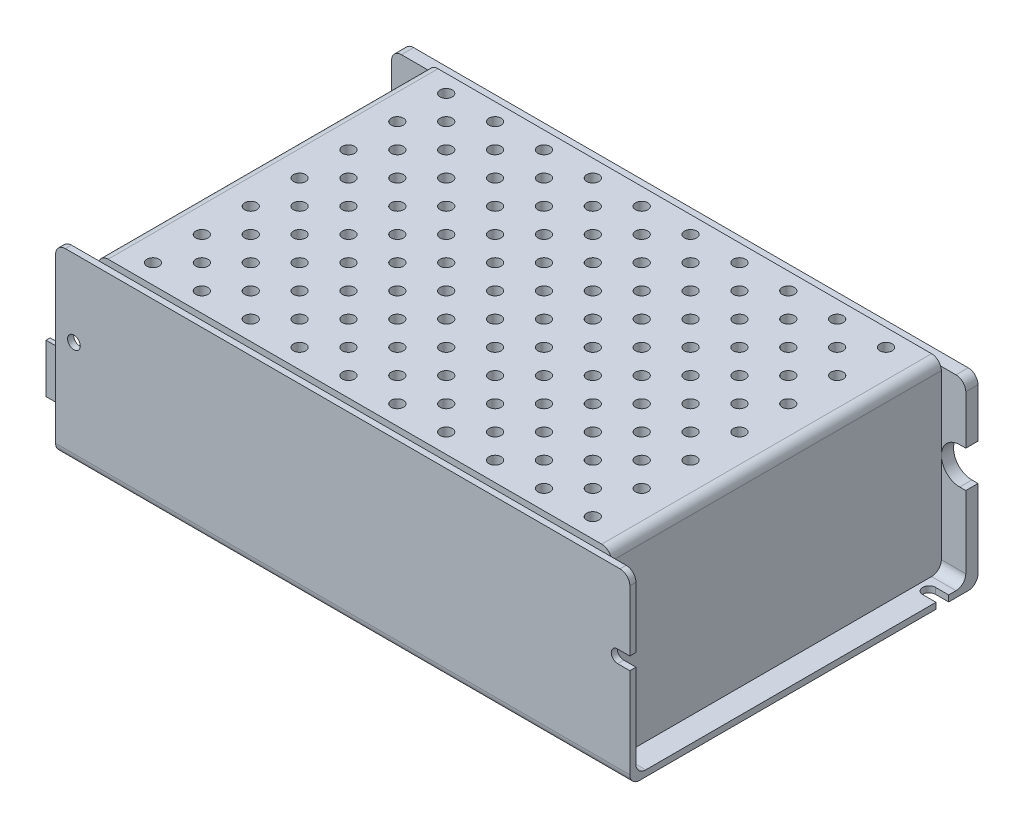
SolidWorks part; units mm, degrees
ref_plane "Front Plane" through (0, 0, 0) normal (0, 0, 1) x (1, 0, 0)
ref_plane "Top Plane" through (0, 0, 0) normal (0, 1, 0) x (1, 0, 0)
ref_plane "Right Plane" through (0, 0, 0) normal (1, 0, 0) x (0, 0, -1)
sketch "Sketch1" plane through (0, 0, 0) normal (0, 1, 0) x (1, 0, 0)
  line L0 (-66.675, 42.8625) -> (66.675, -42.8625) construction
  line L1 (-66.675, 42.8625) -> (66.675, 42.8625)
  line L2 (-66.675, 42.8625) -> (-66.675, -42.8625)
  line L3 (-66.675, -42.8625) -> (66.675, -42.8625)
  line L4 (66.675, 42.8625) -> (66.675, -42.8625)
  line L5 (66.675, 42.8625) -> (-66.675, -42.8625) construction
  dimension "D1" = 133.35
  dimension "D2" = 85.725
extrude "Boss-Extrude1" add sketch "Sketch1" along normal blind 47.625
ref_plane "Plane1" through (73.025, 0, 0) normal (1, 0, 0) x (0, 0, -1)
sketch "Sketch2" plane through (73.025, 0, 0) normal (1, 0, 0) x (0, 0, -1)
  line L0 (-42.8625, 46.0375) -> (-44.45, 46.0375)
  line L1 (-42.8625, 47.625) -> (-42.8625, 0) construction
  line L2 (-44.45, 46.0375) -> (-44.45, -1.5875)
  line L3 (-44.45, -1.5875) -> (46.0375, -1.5875)
  line L4 (46.0375, -1.5875) -> (46.0375, 46.0375)
  line L5 (46.0375, 46.0375) -> (42.8625, 46.0375)
  line L6 (42.8625, 47.625) -> (42.8625, 0) construction
  line L7 (-44.45, 22.225) -> (-42.8625, 22.225) construction
  line L8 (6.5777, 0) -> (6.5777, -1.5875) construction
  line L9 (-42.8625, 0) -> (42.8625, 0) construction
  line L10 (42.8625, 13.1605) -> (44.45, 13.1605) construction
  line L11 (44.45, 13.1605) -> (46.0375, 13.1605) construction
  line L12 (-42.8625, 46.0375) -> (-42.8625, 0)
  line L13 (-42.8625, 0) -> (42.8625, 0)
  line L14 (42.8625, 0) -> (42.8625, 46.0375)
  dimension "D1" = 1.5875
  dimension "D2" = 47.625
extrude "Boss-Extrude2" add sketch "Sketch2" against normal blind 149.225
sketch "Sketch3" plane through (0, 0, 0) normal (0, 1, 0) x (1, 0, 0)
  line L0 (73.025, 38.4175) -> (69.5811, 38.4175)
  line L1 (73.025, -26.1938) -> (73.025, 26.1938) construction
  line L2 (73.025, 35.1155) -> (69.5811, 35.1155)
  line L3 (-76.2, 46.0375) -> (73.025, 46.0375) construction
  line L4 (73.025, 38.4175) -> (73.025, 35.1155)
  line L5 (-76.2, -44.45) -> (73.025, -44.45) construction
  line L6 (-76.2, 42.8625) -> (-76.2, -42.8625) construction
  line L7 (-76.2, 14.9685) -> (-71.4375, 10.206)
  line L8 (-71.4375, 10.206) -> (-71.4375, -34.244)
  line L9 (-71.4375, -34.244) -> (-76.2, -39.0065)
  line L10 (-76.2, -39.0065) -> (-76.2, 14.9685)
  arc A0 (69.5811, 35.1155) -> (69.5811, 38.4175) centre (69.5811, 36.7665) cw
  circle A1 centre (-71.4375, -38.1) radius 1.651
  dimension "D1" = 3.302
  dimension "D3" = 3.302
  dimension "D2" = 7.62
  dimension "D4" = 6.35
  dimension "D5" = 4.7625
  dimension "D6" = 44.45
  dimension "D7" = 53.975
  dimension "D8" = 4.7625
extrude "Cut-Extrude1" cut sketch "Sketch3" against normal through all
sketch "Sketch4" plane through (-66.675, 0, 0) normal (-1, 0, 0) x (0, 0, 1)
  line L0 (12.019, -1.5875) -> (12.019, 3.175) construction
  line L1 (-13.381, 15.875) -> (37.419, 15.875)
  line L2 (-13.381, 15.875) -> (-13.381, 3.175)
  line L3 (-13.381, 3.175) -> (37.419, 3.175)
  line L4 (37.419, 15.875) -> (37.419, 3.175)
  line L5 (34.244, -1.5875) -> (-10.206, -1.5875) construction
  dimension "D1" = 50.8
  dimension "D2" = 12.7
  dimension "D3" = 4.7625
extrude "Boss-Extrude3" add sketch "Sketch4" along normal blind 19.05
sketch "Sketch5" plane through (0, 15.875, 0) normal (0, 1, 0) x (1, 0, 0)
  line L0 (-85.725, -37.419) -> (-85.725, 13.381) construction
  line L1 (-85.725, 12.3226) -> (-76.2, 12.3226)
  line L2 (-85.725, 12.3226) -> (-85.725, 3.4326)
  line L3 (-85.725, 3.4326) -> (-76.2, 3.4326)
  line L4 (-76.2, 12.3226) -> (-76.2, 3.4326)
  line L5 (-80.9625, 12.3226) -> (-80.9625, 13.381) construction
  line L6 (-85.725, 2.3743) -> (-76.2, 2.3743)
  line L7 (-85.725, 2.3743) -> (-85.725, -6.5157)
  line L8 (-85.725, -6.5157) -> (-76.2, -6.5157)
  line L9 (-76.2, 2.3743) -> (-76.2, -6.5157)
  line L10 (-85.725, -7.574) -> (-76.2, -7.574)
  line L11 (-85.725, -7.574) -> (-85.725, -16.464)
  line L12 (-85.725, -16.464) -> (-76.2, -16.464)
  line L13 (-76.2, -7.574) -> (-76.2, -16.464)
  line L14 (-85.725, -17.5224) -> (-76.2, -17.5224)
  line L15 (-85.725, -17.5224) -> (-85.725, -26.4124)
  line L16 (-85.725, -26.4124) -> (-76.2, -26.4124)
  line L17 (-76.2, -17.5224) -> (-76.2, -26.4124)
  line L18 (-85.725, -27.4707) -> (-76.2, -27.4707)
  line L19 (-85.725, -27.4707) -> (-85.725, -36.3607)
  line L20 (-85.725, -36.3607) -> (-76.2, -36.3607)
  line L21 (-76.2, -27.4707) -> (-76.2, -36.3607)
  line L22 (-85.725, 13.381) -> (-66.675, 13.381) construction
  line L23 (-80.9625, 3.4326) -> (-80.9625, 2.3743) construction
  line L24 (-76.2, -36.3607) -> (-76.2, -37.419) construction
  line L25 (-80.9625, -6.5157) -> (-80.9625, -7.574) construction
  line L26 (-85.725, -37.419) -> (-66.675, -37.419) construction
  line L27 (-80.9625, -16.464) -> (-80.9625, -17.5224) construction
  line L28 (-80.9625, -26.4124) -> (-80.9625, -27.4707) construction
  line L29 (-80.9625, -36.3607) -> (-80.9625, -37.419) construction
  line L30 (-76.2, 42.8625) -> (-76.2, 14.9685) construction
  line L31 (-80.9625, -7.574) -> (-80.9625, -16.464) construction
  line L32 (-76.2, -12.019) -> (-80.9625, -12.0095) construction
  dimension "D1" = 8.89
extrude "Cut-Extrude2" cut sketch "Sketch5" against normal through all
sketch "Sketch6" plane through (0, 0, -46.0375) normal (0, 0, -1) x (-1, 0, 0)
  line L0 (-73.025, 30.7975) -> (-71.4375, 30.7975)
  line L1 (-73.025, -1.5875) -> (-73.025, 46.0375) construction
  line L2 (-73.025, 21.2725) -> (-71.4375, 21.2725)
  line L3 (74.6125, 30.7975) -> (76.2, 30.7975)
  line L4 (76.2, -1.5875) -> (76.2, 46.0375) construction
  line L5 (74.6125, 21.2725) -> (76.2, 21.2725)
  line L6 (-73.025, 30.7975) -> (-73.025, 21.2725)
  line L7 (76.2, 30.7975) -> (76.2, 21.2725)
  line L8 (76.2, 46.0375) -> (-73.025, 46.0375) construction
  line L9 (-66.675, 46.0375) -> (-66.675, 26.035) construction
  arc A0 (-71.4375, 30.7975) -> (-71.4375, 21.2725) centre (-71.4375, 26.035) cw
  arc A1 (74.6125, 30.7975) -> (74.6125, 21.2725) centre (74.6125, 26.035) ccw
  dimension "D1" = 9.525
  dimension "D2" = 15.24
extrude "Cut-Extrude3" cut sketch "Sketch6" against normal up to next
sketch "Sketch7" plane through (0, 0, 44.45) normal (0, 0, 1) x (1, 0, 0)
  line L0 (-76.2, 26.035) -> (73.025, 26.035) construction
  line L1 (-76.2, 30.7975) -> (-76.2, 21.2725) construction
  line L2 (73.025, 30.7975) -> (73.025, 21.2725) construction
  line L3 (73.025, 27.686) -> (69.85, 27.686)
  line L4 (73.025, 46.0375) -> (73.025, -1.5875) construction
  line L5 (73.025, 24.384) -> (69.85, 24.384)
  line L6 (73.025, 27.686) -> (73.025, 24.384)
  line L7 (-76.2, 46.0375) -> (-76.2, -1.5875) construction
  circle A0 centre (-71.4375, 26.035) radius 1.651
  arc A1 (69.85, 27.686) -> (69.85, 24.384) centre (69.85, 26.035) ccw
  dimension "D1" = 3.302
  dimension "D2" = 4.7625
  dimension "D3" = 3.175
extrude "Cut-Extrude4" cut sketch "Sketch7" against normal up to next
fillet "Fillet1" radius 2.54 6 edges at (-66.675, 47.625, 0) (66.675, 47.625, 0) (73.025, 46.0375, 43.6563) (73.025, 46.0375, -44.45) (-76.2, 46.0375, 43.6563) (-76.2, 46.0375, -44.45)
fillet "Fillet2" radius 2.54 6 edges at (69.85, 0, -42.8625) (69.85, 0, 42.8625) (-71.4375, 0, 42.8625) (-71.4375, 0, -42.8625) (-1.5875, -1.5875, 44.45) (-1.5875, -1.5875, -46.0375)
sketch "Sketch8" plane through (0, 47.625, 0) normal (0, 1, 0) x (1, 0, 0)
  line L0 (-57.5113, 38.3703) -> (-57.5113, 25.6703) construction
  line L1 (-51.1613, 32.0203) -> (-38.4613, 32.0203) construction
  line L2 (-57.5113, 38.3703) -> (-44.8113, 25.6703) construction
  circle A0 centre (-57.5113, 38.3703) radius 1.5875
  circle A1 centre (-44.8113, 38.3703) radius 1.5875
  circle A2 centre (-32.1113, 38.3703) radius 1.5875
  circle A3 centre (-19.4113, 38.3703) radius 1.5875
  circle A4 centre (-6.7113, 38.3703) radius 1.5875
  circle A5 centre (5.9887, 38.3703) radius 1.5875
  circle A6 centre (18.6887, 38.3703) radius 1.5875
  circle A7 centre (31.3887, 38.3703) radius 1.5875
  circle A8 centre (44.0887, 38.3703) radius 1.5875
  circle A9 centre (56.7887, 38.3703) radius 1.5875
  circle A10 centre (-44.8113, 25.6703) radius 1.5875
  circle A11 centre (-32.1113, 25.6703) radius 1.5875
  circle A12 centre (-19.4113, 25.6703) radius 1.5875
  circle A13 centre (-6.7113, 25.6703) radius 1.5875
  circle A14 centre (5.9887, 25.6703) radius 1.5875
  circle A15 centre (18.6887, 25.6703) radius 1.5875
  circle A16 centre (31.3887, 25.6703) radius 1.5875
  circle A17 centre (44.0887, 25.6703) radius 1.5875
  circle A18 centre (56.7887, 25.6703) radius 1.5875
  circle A19 centre (-44.8113, 12.9703) radius 1.5875
  circle A20 centre (-32.1113, 12.9703) radius 1.5875
  circle A21 centre (-19.4113, 12.9703) radius 1.5875
  circle A22 centre (-6.7113, 12.9703) radius 1.5875
  circle A23 centre (5.9887, 12.9703) radius 1.5875
  circle A24 centre (18.6887, 12.9703) radius 1.5875
  circle A25 centre (31.3887, 12.9703) radius 1.5875
  circle A26 centre (44.0887, 12.9703) radius 1.5875
  circle A27 centre (56.7887, 12.9703) radius 1.5875
  circle A28 centre (-44.8113, 0.2703) radius 1.5875
  circle A29 centre (-32.1113, 0.2703) radius 1.5875
  circle A30 centre (-19.4113, 0.2703) radius 1.5875
  circle A31 centre (-6.7113, 0.2703) radius 1.5875
  circle A32 centre (5.9887, 0.2703) radius 1.5875
  circle A33 centre (18.6887, 0.2703) radius 1.5875
  circle A34 centre (31.3887, 0.2703) radius 1.5875
  circle A35 centre (44.0887, 0.2703) radius 1.5875
  circle A36 centre (56.7887, 0.2703) radius 1.5875
  circle A37 centre (-44.8113, -12.4297) radius 1.5875
  circle A38 centre (-32.1113, -12.4297) radius 1.5875
  circle A39 centre (-19.4113, -12.4297) radius 1.5875
  circle A40 centre (-6.7113, -12.4297) radius 1.5875
  circle A41 centre (5.9887, -12.4297) radius 1.5875
  circle A42 centre (18.6887, -12.4297) radius 1.5875
  circle A43 centre (31.3887, -12.4297) radius 1.5875
  circle A44 centre (44.0887, -12.4297) radius 1.5875
  circle A45 centre (56.7887, -12.4297) radius 1.5875
  circle A46 centre (-44.8113, -25.1297) radius 1.5875
  circle A47 centre (-32.1113, -25.1297) radius 1.5875
  circle A48 centre (-19.4113, -25.1297) radius 1.5875
  circle A49 centre (-6.7113, -25.1297) radius 1.5875
  circle A50 centre (5.9887, -25.1297) radius 1.5875
  circle A51 centre (18.6887, -25.1297) radius 1.5875
  circle A52 centre (31.3887, -25.1297) radius 1.5875
  circle A53 centre (44.0887, -25.1297) radius 1.5875
  circle A54 centre (56.7887, -25.1297) radius 1.5875
  circle A55 centre (-44.8113, -37.8297) radius 1.5875
  circle A56 centre (-32.1113, -37.8297) radius 1.5875
  circle A57 centre (-19.4113, -37.8297) radius 1.5875
  circle A58 centre (-6.7113, -37.8297) radius 1.5875
  circle A59 centre (5.9887, -37.8297) radius 1.5875
  circle A60 centre (18.6887, -37.8297) radius 1.5875
  circle A61 centre (31.3887, -37.8297) radius 1.5875
  circle A62 centre (44.0887, -37.8297) radius 1.5875
  circle A63 centre (56.7887, -37.8297) radius 1.5875
  circle A64 centre (-57.5113, 25.6703) radius 1.5875
  circle A65 centre (-57.5113, 12.9703) radius 1.5875
  circle A66 centre (-57.5113, 0.2703) radius 1.5875
  circle A67 centre (-57.5113, -12.4297) radius 1.5875
  circle A68 centre (-57.5113, -25.1297) radius 1.5875
  circle A69 centre (-57.5113, -37.8297) radius 1.5875
  circle A70 centre (-51.1613, 32.0203) radius 1.5875
  circle A71 centre (-38.4613, 32.0203) radius 1.5875
  circle A72 centre (-25.7613, 32.0203) radius 1.5875
  circle A73 centre (-13.0613, 32.0203) radius 1.5875
  circle A74 centre (-0.3613, 32.0203) radius 1.5875
  circle A75 centre (12.3387, 32.0203) radius 1.5875
  circle A76 centre (25.0387, 32.0203) radius 1.5875
  circle A77 centre (37.7387, 32.0203) radius 1.5875
  circle A78 centre (50.4387, 32.0203) radius 1.5875
  circle A79 centre (-38.4613, 19.3203) radius 1.5875
  circle A80 centre (-25.7613, 19.3203) radius 1.5875
  circle A81 centre (-13.0613, 19.3203) radius 1.5875
  circle A82 centre (-0.3613, 19.3203) radius 1.5875
  circle A83 centre (12.3387, 19.3203) radius 1.5875
  circle A84 centre (25.0387, 19.3203) radius 1.5875
  circle A85 centre (37.7387, 19.3203) radius 1.5875
  circle A86 centre (50.4387, 19.3203) radius 1.5875
  circle A87 centre (-38.4613, 6.6203) radius 1.5875
  circle A88 centre (-25.7613, 6.6203) radius 1.5875
  circle A89 centre (-13.0613, 6.6203) radius 1.5875
  circle A90 centre (-0.3613, 6.6203) radius 1.5875
  circle A91 centre (12.3387, 6.6203) radius 1.5875
  circle A92 centre (25.0387, 6.6203) radius 1.5875
  circle A93 centre (37.7387, 6.6203) radius 1.5875
  circle A94 centre (50.4387, 6.6203) radius 1.5875
  circle A95 centre (-38.4613, -6.0797) radius 1.5875
  circle A96 centre (-25.7613, -6.0797) radius 1.5875
  circle A97 centre (-13.0613, -6.0797) radius 1.5875
  circle A98 centre (-0.3613, -6.0797) radius 1.5875
  circle A99 centre (12.3387, -6.0797) radius 1.5875
  circle A100 centre (25.0387, -6.0797) radius 1.5875
  circle A101 centre (37.7387, -6.0797) radius 1.5875
  circle A102 centre (50.4387, -6.0797) radius 1.5875
  circle A103 centre (-38.4613, -18.7797) radius 1.5875
  circle A104 centre (-25.7613, -18.7797) radius 1.5875
  circle A105 centre (-13.0613, -18.7797) radius 1.5875
  circle A106 centre (-0.3613, -18.7797) radius 1.5875
  circle A107 centre (12.3387, -18.7797) radius 1.5875
  circle A108 centre (25.0387, -18.7797) radius 1.5875
  circle A109 centre (37.7387, -18.7797) radius 1.5875
  circle A110 centre (50.4387, -18.7797) radius 1.5875
  circle A111 centre (-38.4613, -31.4797) radius 1.5875
  circle A112 centre (-25.7613, -31.4797) radius 1.5875
  circle A113 centre (-13.0613, -31.4797) radius 1.5875
  circle A114 centre (-0.3613, -31.4797) radius 1.5875
  circle A115 centre (12.3387, -31.4797) radius 1.5875
  circle A116 centre (25.0387, -31.4797) radius 1.5875
  circle A117 centre (37.7387, -31.4797) radius 1.5875
  circle A118 centre (50.4387, -31.4797) radius 1.5875
  circle A119 centre (-51.1613, 19.3203) radius 1.5875
  circle A120 centre (-51.1613, 6.6203) radius 1.5875
  circle A121 centre (-51.1613, -6.0797) radius 1.5875
  circle A122 centre (-51.1613, -18.7797) radius 1.5875
  circle A123 centre (-51.1613, -31.4797) radius 1.5875
  dimension "D7" = 3.175
  dimension "D3" = 12.7
  dimension "D6" = 12.7
  dimension "D1" = 10
  dimension "D2" = 7
  dimension "D4" = 9
  dimension "D5" = 6
extrude "Cut-Extrude5" cut sketch "Sketch8" against normal blind 5.08
